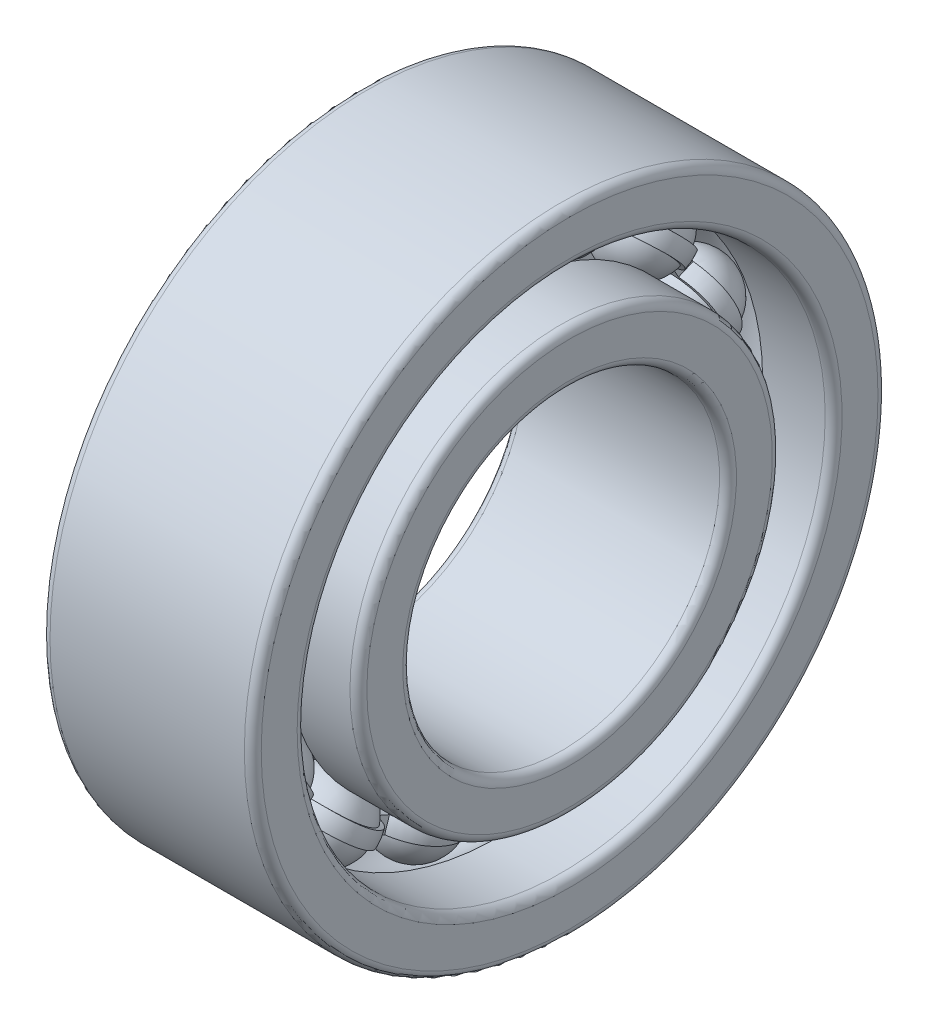
SolidWorks part; units mm, degrees
material "AISI 304"
ref_plane "前视基准面" through (0, 0, 0) normal (0, 0, 1) x (1, 0, 0)
ref_plane "上视基准面" through (0, 0, 0) normal (0, 1, 0) x (1, 0, 0)
ref_plane "右视基准面" through (0, 0, 0) normal (1, 0, 0) x (0, 0, -1)
sketch "尺寸草图" plane through (0, 0, 0) normal (0, 0, 1) x (1, 0, 0)
  line L0 (-19.9271, 0) -> (19.9271, 0) construction
  line L1 (0, 21.603) -> (0, -21.603) construction
  line L2 (-0.92, 3) -> (0.92, 3)
  line L3 (1, 2.92) -> (1, 2.58)
  line L4 (-1, 2.92) -> (-1, 2.58)
  line L5 (-0.92, 2.5) -> (0.92, 2.5)
  line L6 (-3.5, 2.25) -> (3.3577, 2.25) construction
  line L7 (-0.92, 2) -> (0.92, 2)
  line L8 (1, 1.92) -> (1, 1.58)
  line L9 (0.92, 1.5) -> (-0.92, 1.5)
  line L10 (-1, 1.58) -> (-1, 1.92)
  line L11 (0, 2.25) -> (0, 2.625) construction
  circle A0 centre (0, 2.25) radius 0.375
  arc A1 (1, 2.58) -> (0.92, 2.5) centre (0.92, 2.58) cw
  arc A2 (1, 1.92) -> (0.92, 2) centre (0.92, 1.92) ccw
  arc A3 (-0.92, 2) -> (-1, 1.92) centre (-0.92, 1.92) ccw
  arc A4 (-0.92, 2.5) -> (-1, 2.58) centre (-0.92, 2.58) cw
  arc A5 (-0.92, 1.5) -> (-1, 1.58) centre (-0.92, 1.58) cw
  arc A6 (0.92, 1.5) -> (1, 1.58) centre (0.92, 1.58) ccw
  arc A7 (1, 2.92) -> (0.92, 3) centre (0.92, 2.92) ccw
  arc A8 (-0.92, 3) -> (-1, 2.92) centre (-0.92, 2.92) ccw
  point P7 (0, 0)
  point P25 (-1, 2)
  point P28 (-1, 2.5)
  point P31 (-1, 1.5)
  point P36 (1, 3)
  point P39 (-1, 3)
  dimension "D1" = 0.125
  dimension "D3" = 0.08
  dimension "B" = 2
  dimension "D2" = 1
  dimension "D" = 6
  dimension "(d)" = 3
  dimension "D5" = 2.25
  dimension "D6" = 0.5
  dimension "D7" = 0.5
sketch "草图2" plane through (0, 0, 0) normal (0, 0, 1) x (1, 0, 0)
  line L6 (0.92, 1.5) -> (-0.92, 1.5) construction
  line L8 (-1, 2.92) -> (-1, 2.58) construction
  line L9 (-0.92, 2.5) -> (0.92, 2.5) construction
  line L10 (-0.92, 3) -> (0.92, 3) construction
  line L11 (1, 2.92) -> (1, 2.58) construction
  line L12 (1, 1.92) -> (1, 1.58) construction
  line L13 (-0.92, 2) -> (0.92, 2) construction
  line L14 (0.92, 1.5) -> (-0.92, 1.5)
  line L15 (-1, 1.58) -> (-1, 1.92) construction
  line L18 (-3.5, 0) -> (3.5, 0) construction
  line L19 (-19.9271, 0) -> (19.9271, 0) construction
  line L20 (-1, 2.92) -> (-1, 2.58)
  line L21 (-0.92, 2.5) -> (-0.2795, 2.5)
  line L22 (-0.92, 3) -> (0.92, 3)
  line L23 (1, 2.92) -> (1, 2.58)
  line L24 (1, 1.92) -> (1, 1.58)
  line L25 (-0.92, 2) -> (-0.2795, 2)
  line L26 (-1, 1.58) -> (-1, 1.92)
  line L27 (0.2795, 2.5) -> (0.92, 2.5)
  line L28 (0.2795, 2) -> (0.92, 2)
  circle A0 centre (0, 2.25) radius 0.375 construction
  arc A1 (0.2795, 2.5) -> (-0.2795, 2.5) centre (0, 2.25) ccw
  arc A2 (-0.2795, 2) -> (0.2795, 2) centre (0, 2.25) ccw
  arc A3 (-0.92, 3) -> (-1, 2.92) centre (-0.92, 2.92) ccw construction
  arc A4 (-1, 2.58) -> (-0.92, 2.5) centre (-0.92, 2.58) ccw construction
  arc A5 (1, 2.92) -> (0.92, 3) centre (0.92, 2.92) ccw construction
  arc A6 (0.92, 2.5) -> (1, 2.58) centre (0.92, 2.58) ccw construction
  arc A7 (1, 1.92) -> (0.92, 2) centre (0.92, 1.92) ccw construction
  arc A8 (0.92, 1.5) -> (1, 1.58) centre (0.92, 1.58) ccw construction
  arc A9 (-0.92, 2) -> (-1, 1.92) centre (-0.92, 1.92) ccw construction
  arc A10 (-1, 1.58) -> (-0.92, 1.5) centre (-0.92, 1.58) ccw construction
  arc A11 (-0.92, 3) -> (-1, 2.92) centre (-0.92, 2.92) ccw
  arc A12 (-1, 2.58) -> (-0.92, 2.5) centre (-0.92, 2.58) ccw
  arc A13 (1, 2.92) -> (0.92, 3) centre (0.92, 2.92) ccw
  arc A14 (0.92, 2.5) -> (1, 2.58) centre (0.92, 2.58) ccw
  arc A15 (1, 1.92) -> (0.92, 2) centre (0.92, 1.92) ccw
  arc A16 (0.92, 1.5) -> (1, 1.58) centre (0.92, 1.58) ccw
  arc A17 (-0.92, 2) -> (-1, 1.92) centre (-0.92, 1.92) ccw
  arc A18 (-1, 1.58) -> (-0.92, 1.5) centre (-0.92, 1.58) ccw
revolve "旋转1" add sketch "草图2" angle 360 about L18
sketch "草图5" plane through (0, 0, 0) normal (0, 0, 1) x (1, 0, 0)
  line L1 (-0.1125, 2.175) -> (0.1125, 2.175)
  line L2 (-0.1125, 2.175) -> (-0.1125, 2.325)
  line L3 (-0.1125, 2.325) -> (0.1125, 2.325)
  line L4 (0.1125, 2.175) -> (0.1125, 2.325)
  line L5 (-0.1125, 2.175) -> (0.1125, 2.325) construction
  line L6 (-0.1125, 2.325) -> (0.1125, 2.175) construction
  circle A0 centre (0, 2.25) radius 0.375 construction
  circle A1 centre (0, 2.25) radius 0.375 construction
  point P0 (0, 2.25)
  dimension "D1" = 0.225
  dimension "D2" = 0.15
revolve "旋转3" add sketch "草图5" angle 360 about L0
ref_axis "基准轴1" through (-3.85, 0, 0) along (1, 0, 0)
sketch "草图3" plane through (0, 0, 0) normal (0, 0, 1) x (1, 0, 0)
  line L1 (-0.4125, 2.25) -> (0.4125, 2.25)
  circle A0 centre (0, 2.25) radius 0.375 construction
  circle A1 centre (0, 2.25) radius 0.375 construction
  arc A2 (0.4125, 2.25) -> (-0.4125, 2.25) centre (0, 2.25) ccw
  dimension "D2" = 0.825
revolve "旋转2" add sketch "草图3" angle 360 about L1 region at (0, 2.4251, 0)
pattern_circular "阵列(圆周)5" count 15 over 360 about axis through (-3.85, 0, 0) along (1, 0, 0) of bodies 103
sketch "草图6" plane through (0, 0, 0) normal (0, 0, 1) x (1, 0, 0)
  line L0 (-0.4056, 2.325) -> (0.4056, 2.325)
  line L1 (-3.5, 2.25) -> (1, 2.25) construction
  line L3 (-0.4056, 2.175) -> (0.4056, 2.175)
  line L4 (1, -2.92) -> (1, 2.92) construction
  arc A0 (-0.4056, 2.175) -> (0.4056, 2.175) centre (0, 2.25) ccw
  circle A1 centre (0, 2.25) radius 0.375 construction
  circle A2 centre (0, 2.25) radius 0.375 construction
  arc A3 (0.4056, 2.325) -> (-0.4056, 2.325) centre (0, 2.25) ccw
  dimension "D1" = 0.825
  dimension "D3" = 0.075
  dimension "D4" = 0.075
revolve "切除-旋转1" cut sketch "草图6" angle 360 about L0
sketch "草图7" plane through (0, 0, 0) normal (0, 0, 1) x (1, 0, 0)
  line L0 (-0.375, 2.25) -> (0.375, 2.25)
  line L1 (-1, 0) -> (1, 0) construction
  line L2 (-1, 2.92) -> (-1, -2.92) construction
  line L3 (1, -2.92) -> (1, 2.92) construction
  circle A0 centre (0, 2.25) radius 0.375 construction
  arc A1 (0.375, 2.25) -> (-0.375, 2.25) centre (0, 2.25) ccw
revolve "旋转4" add sketch "草图7" angle 360 about L0
pattern_circular "阵列(圆周)2" count 15 over 360 about axis through (-3.85, 0, 0) along (1, 0, 0) of "旋转4"
